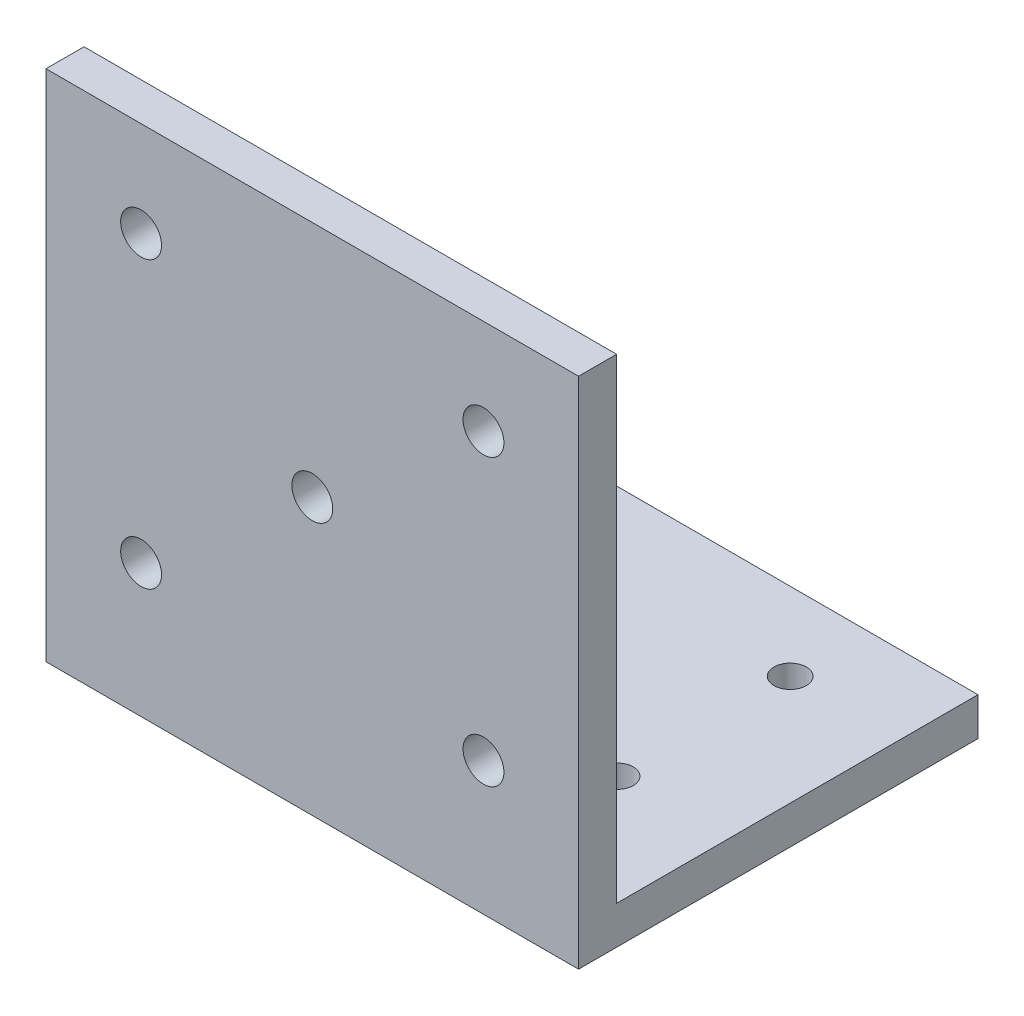
SolidWorks part; units mm, degrees
ref_plane "前视基准面" through (0, 0, 0) normal (0, 0, 1) x (1, 0, 0)
ref_plane "上视基准面" through (0, 0, 0) normal (0, 1, 0) x (1, 0, 0)
ref_plane "右视基准面" through (0, 0, 0) normal (1, 0, 0) x (0, 0, -1)
sketch "草图2" plane through (0, 0, 0) normal (0, 1, 0) x (1, 0, 0)
  line L0 (-34.3123, 12.7907) -> (21.6877, 12.7907)
  line L1 (21.6877, 12.7907) -> (21.6877, -29.2093)
  line L2 (21.6877, -29.2093) -> (-34.3123, -29.2093)
  line L3 (-34.3123, -29.2093) -> (-34.3123, 12.7907)
  line L4 (-14.5123, -29.2093) -> (-14.5123, -8.2093)
  line L5 (-34.3123, -19.6556) -> (-14.5123, -19.6556)
  line L6 (-34.3123, 5.5485) -> (-22.7623, 5.5485)
  line L7 (-22.7623, 12.7907) -> (-22.7623, 0.8907)
  line L8 (-6.3123, 12.7907) -> (-6.3123, -29.2093)
  line L9 (-34.3123, -8.2093) -> (21.6877, -8.2093)
  line L11 (21.6877, -25.2093) -> (-34.3123, -25.2093)
  circle A7 centre (-14.5123, -8.2093) radius 7.2
  circle A8 centre (-22.7623, 0.8907) radius 1.7
  circle A9 centre (10.1377, 0.8907) radius 1.7
  circle A10 centre (-22.7623, -17.3093) radius 1.7
  circle A11 centre (10.1377, -17.3093) radius 1.7
  dimension "D3" = 14.4
  dimension "D4" = 3.4
  dimension "D1" = 56
  dimension "D2" = 42
extrude "凸台-拉伸1" add sketch "草图2" along normal blind 54 contours L1 L11 L8 L2 | L8 L11 L4 L2 | L4 L11 L3 L2 region at (7.6877, 0, 27.2093) region at (-10.4123, 0, 27.2093) region at (-24.4123, 0, 27.2093)
extrude "凸台-拉伸2" add sketch "草图2<3>" along normal blind 4 contours L8 L9 L1 L0 A9 | L7 L0 L3 L6 | A8 L6 L3 L9 A7 L8 L0 L7 | L11 L1 L9 L8 A11 | A7 L4 L11 L8 L9 | L11 L4 L5 L3 | A7 L9 L3 L5 L4 A10 | A7 | A8 | A11 | A9 | A10 region at (-28.5373, 0, -9.1696) region at (-19.7373, 0, -2.3958) region at (7.6493, 0, -2.3127) region at (-26.0728, 0, 14.3732) region at (7.6401, 0, 16.6976) region at (-9.9815, 0, 18.9555) region at (-24.4123, 0, 22.4325)
sketch "草图2<3>" plane through (0, 0, 0) normal (0, 1, 0) x (1, 0, 0) same geometry as "草图2"
sketch "草图3" plane through (0, 0, 25.2093) normal (0, 0, -1) x (-1, 0, 0)
  line L0 (-21.6877, 54) -> (-21.6877, 44)
  line L1 (-21.6877, 54) -> (-21.6877, 4) construction
  line L2 (-21.6877, 44) -> (-11.6877, 44)
  line L3 (6.3123, 54) -> (6.3123, 4)
  line L4 (-21.6877, 54) -> (34.3123, 54) construction
  line L5 (-21.6877, 4) -> (34.3123, 4) construction
  line L6 (-21.6877, 29) -> (34.3123, 29)
  line L7 (34.3123, 54) -> (34.3123, 4) construction
  circle A0 centre (6.3123, 29) radius 2.15
  circle A1 centre (-11.6877, 44) radius 2.15
  circle A2 centre (24.3123, 44) radius 2.15
  circle A3 centre (24.3123, 14) radius 2.15
  circle A4 centre (-11.6877, 14) radius 2.15
  dimension "D1" = 4.3
  dimension "D2" = 4.3
extrude "切除-拉伸1" cut sketch "草图3" against normal blind 4 contours A4 | A1 | A2 | A3 | A0 region at (11.6877, 14, 25.2093)
sketch "草图4" plane through (0, 4, 0) normal (0, 1, 0) x (1, 0, 0)
  line L0 (-22.7623, -15.6093) -> (-22.7623, -13.6093)
  line L1 (-22.7623, 2.5907) -> (-22.7623, 4.5907)
  line L2 (-6.3123, 12.7907) -> (-6.3123, -25.3433)
  line L3 (-22.7623, 2.8907) -> (-11.0565, 2.8907)
  line L4 (-14.5123, 2.8907) -> (-14.5123, 2.6907)
  line L5 (-14.5123, 2.6907) -> (-13.835, 2.6907)
  line L6 (-34.3123, 12.7907) -> (21.6877, 12.7907) construction
  circle A0 centre (10.1377, -17.3093) radius 1.7 construction
  circle A1 centre (10.1377, 0.8907) radius 1.7 construction
  circle A2 centre (-22.7623, -13.6093) radius 1.7
  circle A3 centre (-22.7623, 0.8907) radius 1.7 construction
  circle A4 centre (-22.7623, -17.3093) radius 1.7 construction
  circle A5 centre (10.1377, -17.3093) radius 1.7
  circle A6 centre (10.1377, 0.8907) radius 1.7
  circle A8 centre (-22.7623, 0.8907) radius 1.7
  circle A9 centre (-22.7623, -17.3093) radius 1.7
  circle A10 centre (-22.7623, 4.5907) radius 1.7
  circle A13 centre (-14.5123, -4.5093) radius 7.2
  circle A15 centre (10.1377, 4.5907) radius 1.7
  circle A17 centre (10.1377, -13.6093) radius 1.7
extrude "切除-拉伸3" cut sketch "草图4" against normal blind 10 contours A2 | A15 | A17 | A13 | A10 region at (-23.9304, 4, 12.4412) region at (-14.5123, 4, 4.5093) region at (10.1377, 4, -4.5907) region at (10.1377, 4, 13.6093)
